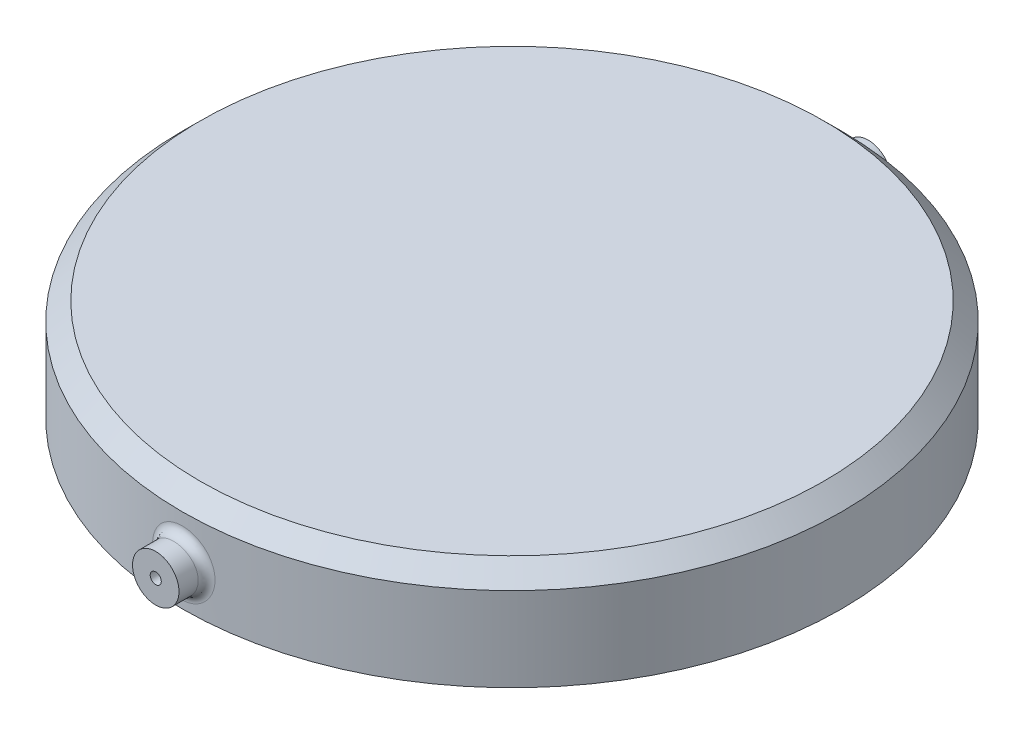
SolidWorks part; units mm, degrees
ref_plane "Front Plane" through (0, 0, 0) normal (0, 0, 1) x (1, 0, 0)
ref_plane "Top Plane" through (0, 0, 0) normal (0, 1, 0) x (1, 0, 0)
ref_plane "Right Plane" through (0, 0, 0) normal (1, 0, 0) x (0, 0, -1)
sketch "Sketch1" plane through (0, 0, 0) normal (0, 1, 0) x (1, 0, 0)
  line L0 (0, 0) -> (0, 13.7725) construction
  line L1 (0, 0) -> (-10.9504, 0) construction
  circle A0 centre (0, 0) radius 35.5
  circle A1 centre (0, 0) radius 35 construction
  circle A2 centre (0, 0) radius 37.25
  circle A3 centre (0, 0) radius 30
  dimension "D1" = 71
  dimension "D2" = 70
  dimension "D3" = 1.75
  dimension "D4" = 60
extrude "Boss-Extrude1" add sketch "Sketch1" against normal blind 10 contours A2 A0 region at (-36.1964, 0, 0)
extrude "Boss-Extrude2" add sketch "Sketch1<2>" along normal blind 1.5 contours A0 | A2 A0 | A3 region at (-34.4959, 0, 0) region at (-36.1964, 0, 0) region at (0, 0, 0)
sketch "Sketch1<2>" plane through (0, 0, 0) normal (0, 1, 0) x (1, 0, 0) same geometry as "Sketch1"
chamfer "Chamfer1" distance 1.5 angle 45 1 edges at (0, 0, 35.5)
chamfer "Chamfer2" distance 2 angle 45 1 edges at (0, 1.5, 37.25)
ref_plane "Plane1" through (0, 0, 37.25) normal (0, 0, 1) x (1, 0, 0)
sketch "Sketch2" plane through (0, 0, 37.25) normal (0, 0, 1) x (1, 0, 0)
  line L0 (0, -0.5) -> (0, -10) construction
  line L1 (-37.25, -0.5) -> (37.25, -0.5) construction
  line L2 (-37.25, -10) -> (37.25, -10) construction
  circle A0 centre (0, -5.5) radius 0.625
  circle A1 centre (0, -5.5) radius 2.625
  dimension "D1" = 1.25
  dimension "D2" = 2
  dimension "D3" = 5
extrude "Cut-Extrude1" cut sketch "Sketch2" against normal blind 10 contours L0 A0 | A0 L0 region at (0.2653, -5.5, 37.25) region at (-0.2653, -5.5, 37.25)
extrude "Boss-Extrude4" add sketch "Sketch2<3>" along normal blind 3 and the other way blind 1 contours A1 L0 A0 | L0 A1 A0 region at (1.1651, -5.5, 37.25) region at (-1.1651, -5.5, 37.25)
sketch "Sketch2<3>" plane through (0, 0, 37.25) normal (0, 0, 1) x (1, 0, 0) same geometry as "Sketch2"
mirror "Mirror1" about plane through (0, 0, 0) normal (0, 0, 1) of "Boss-Extrude4", "Cut-Extrude1"
ref_plane "Plane2" through (37.25, 0, 0) normal (1, 0, 0) x (0, 0, -1)
sketch "tirangle" plane through (37.25, 0, 0) normal (1, 0, 0) x (0, 0, -1)
  line L0 (0, -0.5) -> (0, -13.8889) construction
  line L2 (2.5, -0.5) -> (-2.5, -0.5)
  line L6 (-2.5, -0.5) -> (0, -3)
  line L7 (-37.25, -0.5) -> (37.25, -0.5) construction
  line L8 (0, -3) -> (2.5, -0.5)
  dimension "D1" = 45
  dimension "D2" = 5
fillet "Fillet1" radius 1 2 edges at (2.5563, -4.9036, -37.1622) (-0.5964, -2.9437, 37.2452)
